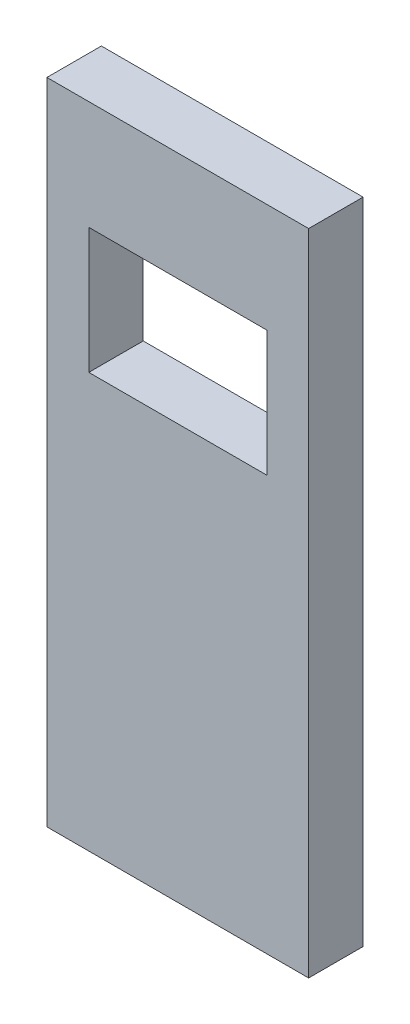
SolidWorks part; units mm, degrees
ref_plane "Front Plane" through (0, 0, 0) normal (0, 0, 1) x (1, 0, 0)
ref_plane "Top Plane" through (0, 0, 0) normal (0, 1, 0) x (1, 0, 0)
ref_plane "Right Plane" through (0, 0, 0) normal (1, 0, 0) x (0, 0, -1)
sketch "Sketch1" plane through (0, 0, 0) normal (0, 0, 1) x (1, 0, 0)
  line L0 (0, 62) -> (0, 39.6)
  line L1 (0, 62) -> (25, 62)
  line L2 (0, 39.6) -> (0, 34.4)
  line L3 (25, 0) -> (0, 0)
  line L4 (4, 51.6) -> (21, 51.6)
  line L5 (4, 39.6) -> (21, 39.6)
  line L6 (4, 51.6) -> (4, 39.6)
  line L7 (21, 51.6) -> (21, 39.6)
  line L8 (0, 39.6) -> (25, 39.6) construction
  line L9 (0, 34.4) -> (25, 34.4) construction
  line L10 (0, 34.4) -> (0, 22.4)
  line L11 (0, 22.4) -> (0, 17.2)
  line L12 (25, 39.6) -> (25, 34.4)
  line L13 (25, 62) -> (25, 39.6)
  line L14 (0, 17.2) -> (0, 0)
  line L15 (25, 34.4) -> (25, 22.4)
  line L16 (25, 22.4) -> (25, 17.2)
  line L17 (25, 17.2) -> (25, 0)
  line L18 (0, 22.4) -> (25, 22.4) construction
  line L19 (25, 17.2) -> (0, 17.2) construction
  line L20 (12.5, -0.0005) -> (12.5, 4.0956) construction
  point P18 (12.5, 39.6)
  point P20 (12.5, 51.6)
  point P21 (12.5, 62)
  dimension "D1" = 10.4
  dimension "D2" = 12
  dimension "D3" = 5.2
  dimension "D4" = 25
  dimension "D5" = 12
  dimension "D6" = 17
  dimension "D7" = 17.2
extrude "Boss-Extrude1" add sketch "Sketch1" along normal mid plane 5.2
